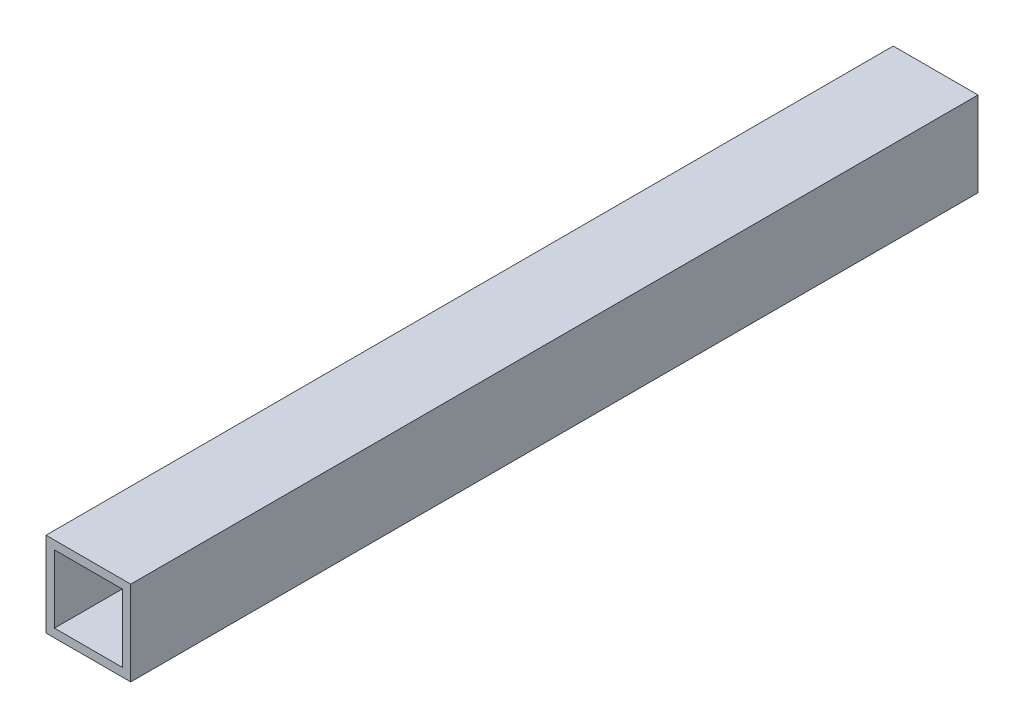
SolidWorks part; units mm, degrees
ref_plane "Front Plane" through (0, 0, 0) normal (0, 0, 1) x (1, 0, 0)
ref_plane "Top Plane" through (0, 0, 0) normal (0, 1, 0) x (1, 0, 0)
ref_plane "Right Plane" through (0, 0, 0) normal (1, 0, 0) x (0, 0, -1)
sketch "Sketch1" plane through (0, 0, 0) normal (0, 0, 1) x (1, 0, 0)
  line L0 (-20, 20) -> (-20, -20)
  line L1 (-25, 25) -> (25, 25)
  line L2 (-25, 25) -> (-25, -25)
  line L3 (-25, -25) -> (25, -25)
  line L4 (25, 25) -> (25, -25)
  line L5 (-20, -20) -> (20, -20)
  line L6 (20, 20) -> (20, -20)
  line L7 (-20, 20) -> (20, 20)
  dimension "tube_width" = 50
  dimension "D1" = 50
  dimension "D3" = 25
  dimension "D4" = 25
  dimension "tube_thickness" = 5
extrude "Boss-Extrude1" add sketch "Sketch1" along normal blind 500
ref_plane "Plane1" through (0, 0, 250) normal (0, 0, 1) x (1, 0, 0)
ref_axis "Axis1" through (0, 27.5, 250) along (0, -1, 0)
equation "\"D1@Sketch1\"= \"tube_width@Sketch1\""
equation "\"D3@Sketch1\"=\"tube_width@Sketch1\"/2"
equation "\"D4@Sketch1\"=\"tube_width@Sketch1\"/2"
